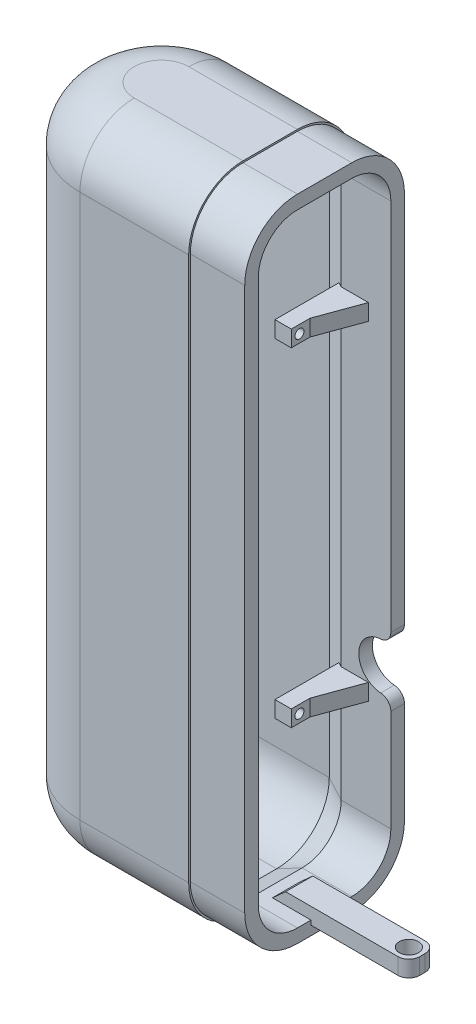
SolidWorks part; units mm, degrees
ref_plane "Front Plane" through (0, 0, 0) normal (0, 0, 1) x (1, 0, 0)
ref_plane "Top Plane" through (0, 0, 0) normal (0, 1, 0) x (1, 0, 0)
ref_plane "Right Plane" through (0, 0, 0) normal (1, 0, 0) x (0, 0, -1)
sketch "Sketch1" plane through (0, 0, 0) normal (0, 1, 0) x (1, 0, 0)
  line L0 (0, 19.05) -> (0, -19.05) construction
  line L1 (0, -19.05) -> (25.4, -19.05)
  line L2 (25.4, -19.05) -> (25.4, 19.05)
  line L3 (25.4, 19.05) -> (0, 19.05)
  arc A0 (0, 19.05) -> (0, -19.05) centre (0, 0) ccw
  dimension "D1" = 38.1
  dimension "D2" = 25.4
extrude "Boss-Extrude1" add sketch "Sketch1" along normal mid plane 152.4
fillet "Fillet1" radius 12.7 6 edges at (12.7, 76.2, -19.05) (12.7, 76.2, 19.05) (12.7, -76.2, -19.05) (12.7, -76.2, 19.05) (-19.05, 76.2, 0) (-19.05, -76.2, 0)
shell "Shell1" thickness 0.4 removed face at (25.4, 0, 0)
sketch "Sketch4" plane through (25.4, 0, 0) normal (1, 0, 0) x (0, 0, -1)
  line L0 (6.35, -75.8) -> (-6.35, -75.8) construction
  line L1 (-18.65, 63.5) -> (-18.65, -63.5) construction
  line L2 (18.65, -63.5) -> (18.65, 63.5) construction
  line L3 (-6.35, 75.8) -> (6.35, 75.8) construction
  line L4 (6.35, -75.8) -> (-6.35, -75.8)
  line L5 (-18.65, 63.5) -> (-18.65, -63.5)
  line L6 (18.65, -63.5) -> (18.65, 63.5)
  line L7 (-6.35, 75.8) -> (6.35, 75.8)
  arc A1 (-18.65, -63.5) -> (-6.35, -75.8) centre (-6.35, -63.5) ccw construction
  arc A2 (6.35, -75.8) -> (18.65, -63.5) centre (6.35, -63.5) ccw construction
  arc A3 (-6.35, 75.8) -> (-18.65, 63.5) centre (-6.35, 63.5) ccw construction
  arc A4 (18.65, 63.5) -> (6.35, 75.8) centre (6.35, 63.5) ccw construction
  arc A5 (-18.65, -63.5) -> (-6.35, -75.8) centre (-6.35, -63.5) ccw
  arc A6 (6.35, -75.8) -> (18.65, -63.5) centre (6.35, -63.5) ccw
  arc A7 (-6.35, 75.8) -> (-18.65, 63.5) centre (-6.35, 63.5) ccw
  arc A8 (18.65, 63.5) -> (6.35, 75.8) centre (6.35, 63.5) ccw
extrude "Extrude-Thin1" add sketch "Sketch4" along normal blind 12.7 and the other way blind 6.35 thin thin type one direction reverse wall 3.175
chamfer "Chamfer1" distance 7.46 angle 28 8 edges at (19.05, 0, -15.475) (19.05, 69.9523, -12.8023) (19.05, -69.9523, -12.8023) (19.05, 72.625, 0) (19.05, -72.625, 0) (19.05, 69.9523, 12.8023) (19.05, -69.9523, 12.8023) (19.05, 0, 15.475) first distance on face at (28.575, 0, -15.475) first distance on face at (28.575, 69.0074, -11.8574) first distance on face at (28.575, -69.0074, -11.8574) first distance on face at (28.575, 72.625, 0) first distance on face at (28.575, -72.625, 0) first distance on face at (28.575, 69.0074, 11.8574) first distance on face at (28.575, -69.0074, 11.8574) first distance on face at (28.575, 0, 15.475)
sketch "Sketch6" plane through (25.4, 0, 0) normal (1, 0, 0) x (0, 0, -1)
  line L1 (1.1107, 40.3365) -> (18.65, 40.3365)
  line L2 (1.1107, 40.3365) -> (1.1107, 36.5265)
  line L3 (1.1107, 36.5265) -> (18.65, 36.5265)
  line L4 (18.65, 40.3365) -> (18.65, 36.5265)
  line L5 (1.1107, -36.506) -> (4.9207, -40.316) construction
  line L6 (1.1107, -36.506) -> (18.65, -36.506)
  line L7 (1.1107, -36.506) -> (1.1107, -40.316)
  line L8 (1.1107, -40.316) -> (18.65, -40.316)
  line L9 (18.65, -36.506) -> (18.65, -40.316)
  line L10 (1.1107, 40.3365) -> (4.9207, 36.5265) construction
  line L11 (18.65, -63.5) -> (18.65, 63.5) construction
  line L12 (18.65, 63.5) -> (18.65, -63.5) construction
  circle A0 centre (3.0157, 38.4315) radius 1.0543 construction
  circle A1 centre (3.0157, -38.411) radius 1.0543 construction
  circle A2 centre (3.0157, 38.4315) radius 1.0543
  circle A3 centre (3.0157, -38.411) radius 1.0543
  point P16 (3.0157, 38.4315)
  point P19 (3.0157, -38.411)
  dimension "D1" = 45
  dimension "D2" = 3.81
extrude "Boss-Extrude3" add sketch "Sketch6" along normal blind 3.81
chamfer "Chamfer2" distance 10 angle 20 2 edges at (29.21, 38.4315, -15.475) (29.21, -38.411, -15.475) first distance on face at (29.21, 38.4315, -4.07) first distance on face at (29.21, -38.411, -4.07)
ref_plane "Plane2" through (0, -73.66, 0) normal (0, -1, 0) x (-1, 0, 0)
sketch "Sketch7" plane through (0, -73.66, 0) normal (0, 1, 0) x (1, 0, 0)
  line L0 (38.1, 6.35) -> (38.1, -6.35) construction
  line L1 (27.94, -3.175) -> (60.96, -3.175)
  line L2 (27.94, -3.175) -> (27.94, 3.175)
  line L3 (27.94, 3.175) -> (60.96, 3.175)
  line L4 (60.96, -3.175) -> (60.96, 3.175)
  line L5 (27.94, -3.175) -> (60.96, 3.175) construction
  line L6 (27.94, 3.175) -> (60.96, -3.175) construction
  point P0 (44.45, 0)
  point P5 (0, 0)
  dimension "D1" = 10.16
  dimension "D2" = 6.35
  dimension "D3" = 22.86
extrude "Boss-Extrude4" add sketch "Sketch7" along normal blind 3.81
chamfer "Chamfer3" distance 3.81 angle 48 1 edges at (27.94, -69.85, 0) first distance on face at (27.94, -71.2375, 0)
sketch "Sketch8" plane through (0, -69.85, 0) normal (0, 1, 0) x (1, 0, 0)
  line L0 (60.96, 3.175) -> (54.61, -3.175) construction
  line L1 (32.1714, -3.175) -> (60.96, -3.175) construction
  circle A0 centre (57.785, 0) radius 2.25
  dimension "D2" = 4.5
  dimension "D1" = 45
extrude "Cut-Extrude1" cut sketch "Sketch8" against normal through all
fillet "Fillet2" radius 2.54 2 edges at (60.96, -71.755, -3.175) (60.96, -71.755, 3.175)
sketch "Sketch9" plane through (0, 0, -15.475) normal (0, 0, 1) x (1, 0, 0)
  circle A0 centre (36.068, -31.75) radius 2.921 construction
  circle A1 centre (36.068, -31.75) radius 2.921 construction
  circle A2 centre (36.068, -31.75) radius 5.461
  dimension "D1" = 2.54
extrude "Cut-Extrude2" cut sketch "Sketch9" against normal through all
fillet "Fillet3" radius 2.54 2 edges at (38.1, -36.8189, -17.0625) (38.1, -26.6811, -17.0625)
